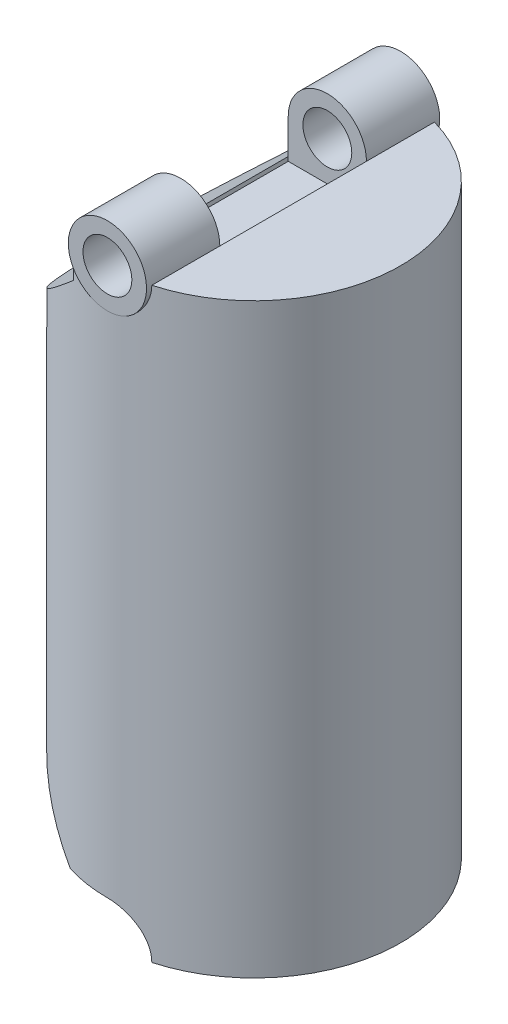
SolidWorks part; units mm, degrees
ref_plane "Alzado" through (0, 0, 0) normal (0, 0, 1) x (1, 0, 0)
ref_plane "Planta" through (0, 0, 0) normal (0, 1, 0) x (1, 0, 0)
ref_plane "Vista lateral" through (0, 0, 0) normal (1, 0, 0) x (0, 0, -1)
sketch "Croquis1" plane through (0, 0, 0) normal (0, 1, 0) x (1, 0, 0)
  circle A0 centre (0, 0) radius 15
  dimension "D1" = 30
extrude "Saliente-Extruir1" add sketch "Croquis1" along normal blind 60
ref_plane "Plano1" through (0, 30, 0) normal (0, 1, 0) x (1, 0, 0)
sketch "Croquis8" plane through (0, 0, 0) normal (0, 0, 1) x (1, 0, 0)
  line L0 (15, 60) -> (-15, 60) construction
  circle A0 centre (0, 60) radius 2.5
  point P4 (0, 0)
  dimension "D1" = 5
  dimension "D2" = 0
extrude "Cortar-Extruir2" cut sketch "Croquis8" against normal mid plane 30
sketch "Croquis9" plane through (0, 0, 0) normal (0, 0, 1) x (1, 0, 0)
  line L12 (0, 56) -> (0, 60) construction
  circle A4 centre (0, 60) radius 4
  circle A5 centre (0, 60) radius 2.5
  dimension "D1" = 4
sketch "Croquis10" plane through (0, 0, 0) normal (0, 0, 1) x (1, 0, 0)
  circle A3 centre (0, 0) radius 4
  dimension "D1" = 8
extrude "Saliente-Extruir3" add sketch "Croquis9" along normal blind 7.5 from offset 7.5
mirror "Simetría2" about plane through (0, 0, 0) normal (0, 0, 1) of "Saliente-Extruir3"
extrude "Saliente-Extruir4" add sketch "Croquis10" along normal mid plane 15
sketch "Croquis12" plane through (0, 0, 7.5) normal (0, 0, 1) x (1, 0, 0)
  circle A0 centre (0, 0) radius 2.5
  dimension "D1" = 5
extrude "Cortar-Extruir4" cut sketch "Croquis12" against normal mid plane 60
sketch "Croquis13" plane through (0, 0, 0) normal (0, 0, 1) x (1, 0, 0)
  circle A0 centre (0, 0) radius 4
extrude "Cortar-Extruir5" cut sketch "Croquis13" along normal blind 30 from offset 7.5
mirror "Simetría3" about plane through (0, 0, 0) normal (0, 0, 1) of "Cortar-Extruir5"
sketch "Croquis7" plane through (0, 0, 0) normal (0, 0, 1) x (1, 0, 0)
  line L1 (0, 60) -> (-15, 46.6235) construction
  line L3 (-4, 56.4329) -> (-15, 46.6235)
  line L5 (-15, 60) -> (-15, 0) construction
  line L6 (-15, 46.6235) -> (-15, 60)
  line L7 (-15, 60) -> (-4, 60)
  line L8 (-4, 60) -> (-4, 56.4329)
extrude "Cortar-Extruir6" cut sketch "Croquis7" against normal mid plane 30
sketch "Croquis14" plane through (-4, 0, 0) normal (-1, 0, 0) x (0, 0, 1)
  line L1 (-7.5, 60) -> (7.5, 60)
  line L2 (-7.5, 60) -> (-7.5, 57.5)
  line L3 (-7.5, 57.5) -> (7.5, 57.5)
  line L4 (7.5, 60) -> (7.5, 57.5)
  dimension "D1" = 2.5
extrude "Cortar-Extruir7" cut sketch "Croquis14" against normal blind 4
mirror "Simetría4" about plane through (0, 30, 0) normal (0, 1, 0) of "Cortar-Extruir6"
sketch "Croquis15" plane through (0, 0, 0) normal (0, 0, 1) x (1, 0, 0)
  line L0 (0, 4) -> (-8.002, 4)
  line L1 (-8.002, 4) -> (-8.002, -4.6585)
  line L3 (-8.002, -4.6585) -> (0, -4.6585)
  line L4 (0, -4.6585) -> (0, -4)
  arc A0 (0, 4) -> (0, -4) centre (0, 0) ccw
extrude "Cortar-Extruir8" cut sketch "Croquis15" against normal mid plane 30
sketch "Croquis16" plane through (0, 0, 0) normal (0, 0, 1) x (1, 0, 0)
  circle A0 centre (0, 60) radius 4
extrude "Cortar-Extruir9" cut sketch "Croquis16" against normal mid plane 15
sketch "Croquis17" plane through (-4, 0, 0) normal (-1, 0, 0) x (0, 0, 1)
  line L0 (7.5, 60) -> (7.5, 56) construction
  line L1 (-7.5, 60) -> (7.5, 60)
  line L2 (-7.5, 60) -> (-7.5, 56)
  line L3 (-7.5, 56) -> (7.5, 56)
  line L4 (7.5, 60) -> (7.5, 56)
  dimension "D1" = 4
extrude "Cortar-Extruir10" cut sketch "Croquis17" against normal blind 4
